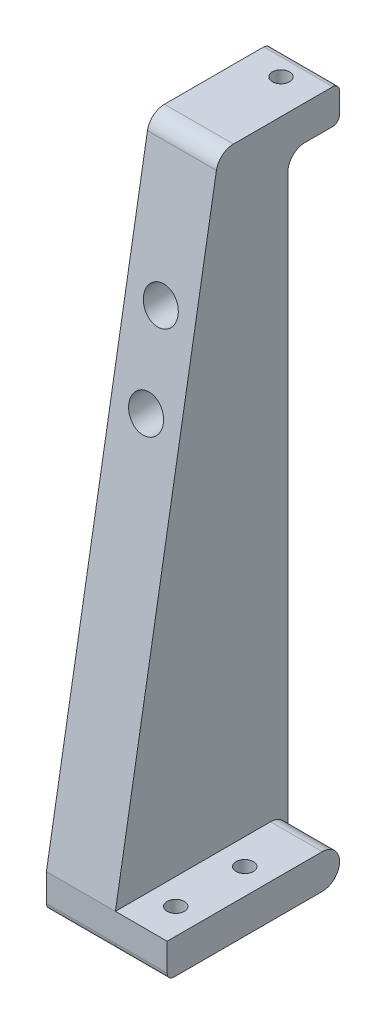
SolidWorks part; units mm, degrees
ref_plane "Front Plane" through (0, 0, 0) normal (0, 0, 1) x (1, 0, 0)
ref_plane "Top Plane" through (0, 0, 0) normal (0, 1, 0) x (1, 0, 0)
ref_plane "Right Plane" through (0, 0, 0) normal (1, 0, 0) x (0, 0, -1)
sketch "Sketch3" plane through (0, 0, 0) normal (1, 0, 0) x (0, 0, -1)
  line L1 (-12.7, -117.837) -> (12.7, -117.837)
  line L2 (-12.7, -117.837) -> (-12.7, -105.137) construction
  line L3 (-12.7, 117.837) -> (12.7, 117.837)
  line L4 (12.7, -117.837) -> (12.7, 117.837)
  line L5 (0, 117.837) -> (0, -117.837) construction
  line L6 (-12.7, 0) -> (12.7, 0) construction
  line L7 (-12.7, -105.137) -> (-50.8, -105.137) construction
  line L8 (-12.7, -105.137) -> (-12.7, -117.837) construction
  line L9 (-12.7, -117.837) -> (-50.8, -117.837)
  line L10 (-50.8, -105.137) -> (-50.8, -117.837)
  line L11 (12.7, 117.837) -> (31.75, 117.837)
  line L12 (12.7, 117.837) -> (12.7, 105.137)
  line L13 (12.7, 105.137) -> (31.75, 105.1369)
  line L14 (31.75, 117.837) -> (31.75, 105.1369)
  line L15 (-12.7, -105.137) -> (-12.7, 0) construction
  line L16 (-12.7, 0) -> (-12.7, 117.837) construction
  line L17 (-12.7, 117.837) -> (-50.8, -105.137)
  point P0 (0, 0)
  dimension "D1" = 235.6739
  dimension "D2" = 19.05
  dimension "D3" = 12.7
  dimension "D4" = 38.1
  dimension "D5" = 12.7
  dimension "D6" = 25.4
extrude "Boss-Extrude1" add sketch "Sketch3" along normal blind 25.4 contours L1 L4 L3 L2 | L7 L10 L9 L2 | L14 L11 L4 L13 region at (0, -12.789, 10.5426) region at (0, -111.487, 31.75) region at (0, 111.487, -22.225)
fillet "Fillet1" radius 6.35 3 edges at (12.7, 105.137, -12.7) (12.7, -117.837, -12.7) (12.7, 117.837, 12.7)
fillet "Fillet3" radius 2.54 3 edges at (12.7, 117.837, -31.75) (12.7, 105.1369, -31.75) (12.7, -117.837, 50.8)
sketch "Sketch9" plane through (0, 117.837, 0) normal (0, 1, 0) x (1, 0, 0)
  line L0 (12.7, 29.21) -> (12.7, 16.51) construction
  line L5 (25.4, 29.21) -> (0, 29.21) construction
  circle A0 centre (12.7, 22.86) radius 3.175
  point P4 (12.7, 22.86)
  dimension "D1" = 6.35
  dimension "D2" = 12.7
extrude "Cut-Extrude2" cut sketch "Sketch9" against normal through all
sketch "Sketch10" plane through (0, 0, -12.7) normal (0, 0, -1) x (-1, 0, 0)
  line L0 (-12.7, 98.787) -> (-12.7, 35.287) construction
  line L1 (0, 98.787) -> (-25.4, 98.787) construction
  circle A0 centre (-12.7, 35.287) radius 3.225
  circle A1 centre (-12.7, 67.037) radius 3.18
  point P4 (-12.7, 67.037)
  dimension "D3" = 6.36
  dimension "D4" = 6.45
  dimension "D1" = 63.5
  dimension "D2" = 31.75
extrude "Cut-Extrude3" cut sketch "Sketch10" against normal through all
ref_plane "Plane2" through (0, 0, 38.1) normal (0, 0, -1) x (-1, 0, 0)
sketch "Sketch18" plane through (0, 0, 38.1) normal (0, 0, -1) x (-1, 0, 0)
  line L0 (-25.4, -111.487) -> (-25.4, 98.787) construction
  line L1 (-25.4, 15.3369) -> (0, 15.3369)
  line L2 (-25.4, 15.3369) -> (-25.4, 88.8369)
  line L3 (-25.4, 88.8369) -> (0, 88.8369)
  line L4 (0, 15.3369) -> (0, 88.8369)
  line L5 (-12.7, 88.8369) -> (-12.7, 15.3369) construction
  line L6 (-25.4, 52.0869) -> (0, 52.0869) construction
  line L7 (-17.9, 15.337) -> (-7.5, 15.337) construction
  line L8 (0, -111.487) -> (0, 98.787) construction
  line L9 (43.05, 88.8369) -> (-13.45, 88.8369) construction
  circle A0 centre (-12.7, 67.037) radius 6.35
  circle A1 centre (-12.7, 35.287) radius 6.35
  point P332 (-12.7, 52.0869)
  dimension "D1" = 12.7
  dimension "D2" = 12.7
extrude "Cut-Extrude4" cut sketch "Sketch18" along normal blind 38.1 contours A0 | A1 region at (12.7, 67.037, 38.1) region at (12.7, 35.287, 38.1)
sketch "Sketch19" plane through (0, -117.837, 0) normal (0, -1, 0) x (1, 0, 0)
  line L0 (25.4, -6.35) -> (25.4, 48.26) construction
  line L1 (25.4, -12.7) -> (44.45, -12.7)
  line L2 (25.4, -12.7) -> (25.4, 50.8)
  line L3 (25.4, 50.8) -> (44.45, 50.8)
  line L4 (44.45, -12.7) -> (44.45, 50.8)
  line L5 (34.925, 50.8) -> (34.925, -12.7) construction
  line L6 (25.4, 19.05) -> (44.45, 19.05) construction
  line L7 (0, 50.8) -> (25.4, 50.8) construction
  line L8 (25.4, -12.7) -> (0, -12.7) construction
  circle A0 centre (34.925, 38.1) radius 3.175
  circle A1 centre (34.925, 12.7) radius 3.175
  point P540 (34.925, 19.05)
  dimension "D4" = 6.35
  dimension "D1" = 19.05
  dimension "D2" = 25.4
  dimension "D3" = 12.7
extrude "Boss-Extrude4" add sketch "Sketch19" against normal blind 12.7
fillet "Fillet6" radius 2.54 1 edges at (34.925, -117.837, 50.8)
fillet "Fillet7" radius 6.35 2 edges at (34.925, -117.837, -12.7) (34.925, -105.1369, -12.7)
equation "\"TestStandHeight\"= 2.52in"
